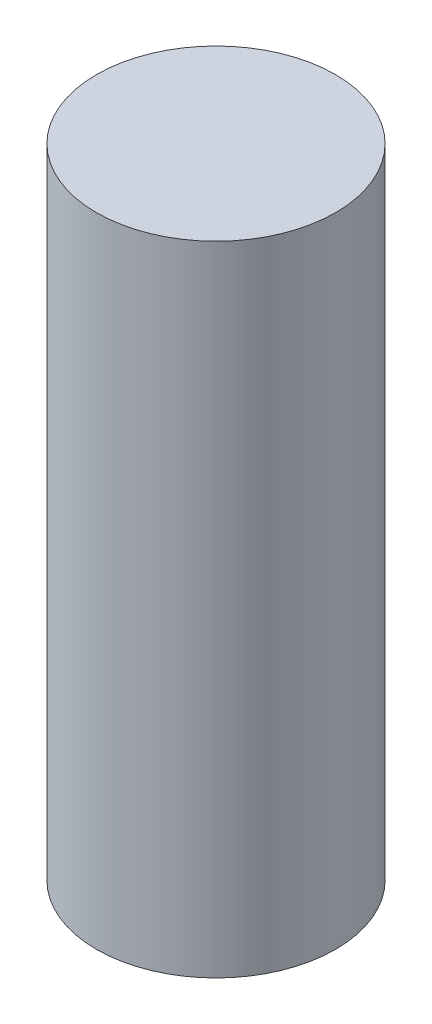
SolidWorks part; units mm, degrees
ref_plane "Front Plane" through (0, 0, 0) normal (0, 0, 1) x (1, 0, 0)
ref_plane "Top Plane" through (0, 0, 0) normal (0, 1, 0) x (1, 0, 0)
ref_plane "Right Plane" through (0, 0, 0) normal (1, 0, 0) x (0, 0, -1)
sketch "Sketch1" plane through (0, 0, 0) normal (0, 1, 0) x (1, 0, 0)
  circle A0 centre (0, 0) radius 2.38
  dimension "D1" = 4.76
extrude "Boss-Extrude1" add sketch "Sketch1" along normal blind 12.7
